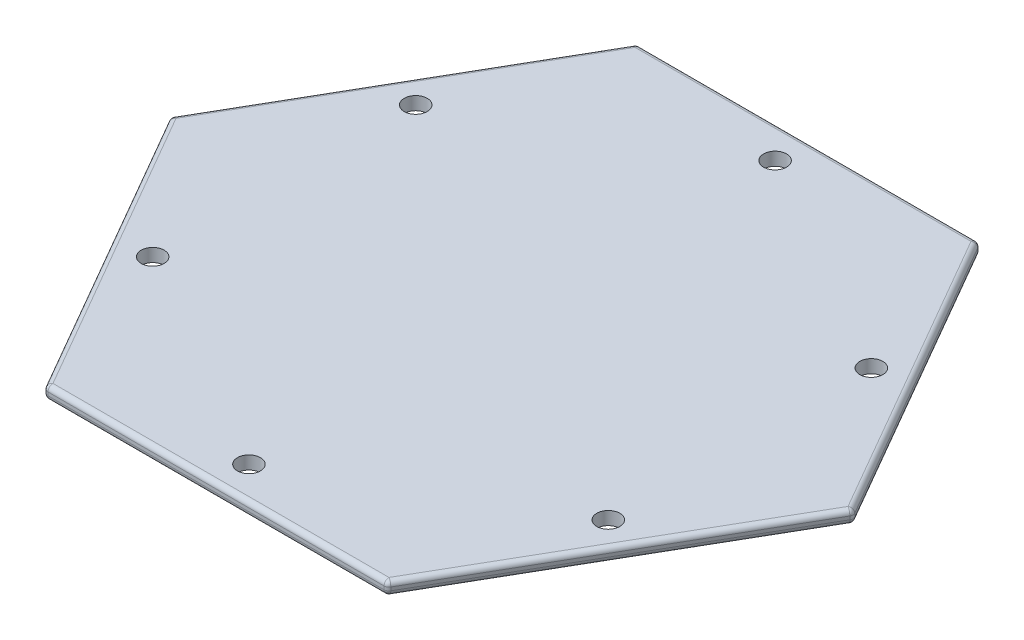
SolidWorks part; units mm, degrees
ref_plane "Front Plane" through (0, 0, 0) normal (0, 0, 1) x (1, 0, 0)
ref_plane "Top Plane" through (0, 0, 0) normal (0, 1, 0) x (1, 0, 0)
ref_plane "Right Plane" through (0, 0, 0) normal (1, 0, 0) x (0, 0, -1)
sketch "Sketch2" plane through (0, 0, 0) normal (0, 1, 0) x (1, 0, 0)
  line L1 (51.9615, 0) -> (25.9808, 45)
  line L2 (25.9808, 45) -> (-25.9808, 45)
  line L3 (-25.9808, 45) -> (-51.9615, 0)
  line L4 (-51.9615, 0) -> (-25.9808, -45)
  line L5 (-25.9808, -45) -> (25.9808, -45)
  line L6 (25.9808, -45) -> (51.9615, 0)
  circle A0 centre (0, 0) radius 45 construction
  dimension "D1" = 90
extrude "Boss-Extrude1" add sketch "Sketch2" along normal blind 2
fillet "Fillet3" radius 0.75 18 edges at (25.9808, 1, 45) (51.9615, 1, 0) (25.9808, 1, -45) (-25.9808, 1, 45) (-25.9808, 1, -45) (-51.9615, 1, 0) (38.9711, 0, -22.5) (0, 0, -45) (-38.9711, 0, -22.5) (-38.9711, 0, 22.5) (0, 0, 45) (38.9711, 0, 22.5) (0, 2, 45) (-38.9711, 2, 22.5) (-38.9711, 2, -22.5) (0, 2, -45) (38.9711, 2, -22.5) (38.9711, 2, 22.5)
sketch "Sketch3" plane through (0, 0, 0) normal (0, 1, 0) x (1, 0, 0)
  circle A0 centre (0, 40) radius 1.75
  circle A1 centre (34.641, 20) radius 1.75
  circle A2 centre (34.641, -20) radius 1.75
  circle A3 centre (0, -40) radius 1.75
  circle A4 centre (-34.641, -20) radius 1.75
  circle A5 centre (-34.641, 20) radius 1.75
  point P16 (0, 0)
  dimension "D1" = 3.5
  dimension "D2" = 40
  dimension "D3" = 6
extrude "Cut-Extrude2" cut sketch "Sketch3" along normal through all and the other way blind 35
sketch "Sketch4" [suppressed] plane through (0, 2, 0) normal (0, 1, 0) x (1, 0, 0)
  line L1 (-10.5, 6) -> (10.5, 6)
  line L2 (-10.5, 6) -> (-10.5, -6)
  line L3 (-10.5, -6) -> (10.5, -6)
  line L4 (10.5, 6) -> (10.5, -6)
  line L5 (-10.5, 6) -> (10.5, -6) construction
  line L6 (-10.5, -6) -> (10.5, 6) construction
  point P0 (0, 0)
  dimension "D1" = 12
  dimension "D2" = 21
extrude "Cut-Extrude3" [suppressed] cut sketch "Sketch4" against normal through all
